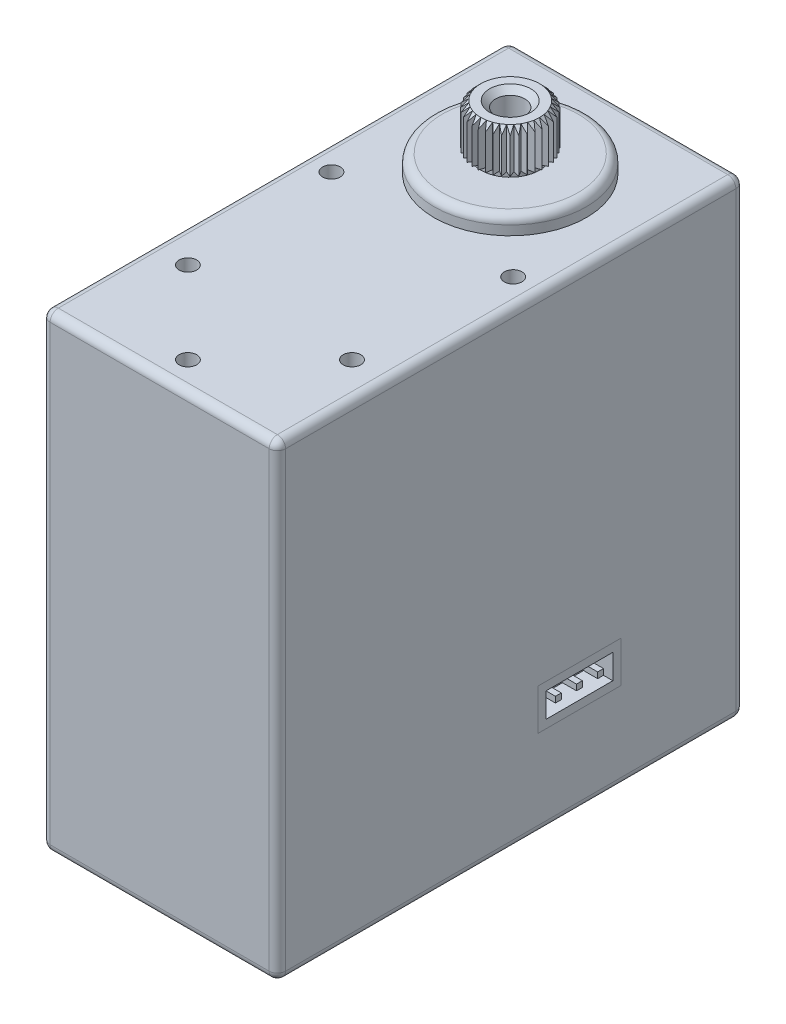
SolidWorks part; units mm, degrees
ref_plane "Alzado" through (0, 0, 0) normal (0, 0, 1) x (1, 0, 0)
ref_plane "Planta" through (0, 0, 0) normal (0, 1, 0) x (1, 0, 0)
ref_plane "Vista lateral" through (0, 0, 0) normal (1, 0, 0) x (0, 0, -1)
sketch "Croquis2" plane through (0, 0, 0) normal (0, 1, 0) x (1, 0, 0)
  line L0 (0, 0) -> (0, -27.5) construction
  line L1 (0, 7.5) -> (0, 9.91) construction
  line L2 (0, -7.5) -> (7.75, -7.5) construction
  line L3 (0, -20.5) -> (7, -20.5) construction
  line L4 (0, 0) -> (0, 7.5) construction
  line L5 (0, 7.5) -> (7.5, 7.5)
  line L6 (0, -27.5) -> (0, -29.91) construction
  line L7 (-10.045, -29.91) -> (10.045, -29.91)
  line L8 (-10.045, 9.91) -> (10.045, 9.91)
  line L9 (10.045, -29.91) -> (10.045, 9.91)
  line L10 (-10.045, -29.91) -> (-10.045, 9.91)
  circle A0 centre (0, 0) radius 3
  circle A3 centre (0, 0) radius 6.5
  circle A4 centre (7, -20.5) radius 0.75
  circle A6 centre (7.5, 7.5) radius 0.75
  circle A10 centre (0, -27.5) radius 0.75
  circle A11 centre (7.75, -7.5) radius 0.75
  circle A13 centre (-7, -20.5) radius 0.75
  circle A14 centre (-7.75, -7.5) radius 0.75
  dimension "D1" = 27.5
  dimension "D2" = 6
  dimension "D3" = 7
  dimension "D4" = 13
  dimension "D7" = 13
  dimension "D5" = 1.5
  dimension "D10" = 1.5
  dimension "D11" = 2.41
  dimension "D12" = 1.5
  dimension "D13" = 2.41
  dimension "D9" = 1.5
  dimension "D6" = 7
  dimension "D8" = 7.5
  dimension "D14" = 10.045
  dimension "D15" = 10.045
  dimension "D16" = 7.75
extrude "Saliente-Extruir1" add sketch "Croquis2" along normal blind 5.4 contours A0 region at (0, 0, 0)
extrude "Saliente-Extruir2" add sketch "Croquis2<4>" along normal blind 1.5 contours A3 region at (-6.3162, 0, 0)
sketch "Croquis2<4>" plane through (0, 0, 0) normal (0, 1, 0) x (1, 0, 0) same geometry as "Croquis2"
extrude "Saliente-Extruir3" add sketch "Croquis2<6>" against normal blind 40 separate body contours L10 L7 L9 L8 A14 A11 A10 A6 A4 A3 A13 | A10 | A4 | A13 | A11 | A14 | A6 | A3 A0 | A0 region at (-0.0202, 0, 11.9783) region at (0, 0, 0) region at (-6.3162, 0, 0) region at (7, 0, 20.5) region at (7.5, 0, -6.7712) region at (0, 0, 27.5) region at (7.75, 0, 7.5) region at (-7, 0, 20.5) region at (-7.75, 0, 7.5)
sketch "Croquis2<6>" plane through (0, 0, 0) normal (0, 1, 0) x (1, 0, 0) same geometry as "Croquis2"
extrude "Cortar-Extruir1" cut sketch "Croquis2<7>" against normal blind 2 contours A10 | A4 | A13 | A14 | A11 region at (7, 0, 20.5) region at (0, 0, 27.5) region at (7.75, 0, 7.5) region at (-7, 0, 20.5) region at (-7.75, 0, 7.5)
sketch "Croquis2<7>" plane through (0, 0, 0) normal (0, 1, 0) x (1, 0, 0) same geometry as "Croquis2"
extrude "Saliente-Extruir4" add sketch "Croquis2<8>" against normal blind 41.5 contours A3
sketch "Croquis2<8>" plane through (0, 0, 0) normal (0, 1, 0) x (1, 0, 0) same geometry as "Croquis2"
extrude "Saliente-Extruir5" add sketch "Croquis2<10>" against normal blind 45.7 contours A0
sketch "Croquis2<10>" plane through (0, 0, 0) normal (0, 1, 0) x (1, 0, 0) same geometry as "Croquis2"
sketch "Croquis3" plane through (0, -40, 0) normal (0, -1, 0) x (1, 0, 0)
  line L0 (0, 0) -> (0, 27.5) construction
  line L1 (0, 27.5) -> (-7.5, 27.5) construction
  line L2 (-7.5, -7.5) -> (-10.045, -7.5) construction
  line L3 (-10.045, 29.91) -> (-10.045, -9.91) construction
  line L4 (-7.5, -7.5) -> (-7.5, -9.91) construction
  line L5 (-10.045, -9.91) -> (10.045, -9.91) construction
  circle A0 centre (-7.5, 12.5) radius 0.75
  circle A1 centre (-7.5, -7.5) radius 0.75
  circle A2 centre (-7.5, 27.5) radius 0.75
  circle A3 centre (7.5, -7.5) radius 0.75
  circle A4 centre (7.5, 12.5) radius 0.75
  circle A5 centre (7.5, 27.5) radius 0.75
  dimension "D3" = 1.5
  dimension "D4" = 1.5
  dimension "D5" = 1.5
  dimension "D1" = 27.5
  dimension "D2" = 7.5
  dimension "D6" = 7.5
  dimension "D7" = 15
  dimension "D8" = 20
  dimension "D9" = 7.5
extrude "Cortar-Extruir2" cut sketch "Croquis3" against normal blind 2
sketch "Croquis5" plane through (0, 0, -9.91) normal (0, 0, -1) x (-1, 0, 0)
  line L0 (-10.045, -40) -> (-10.045, 0) construction
  line L1 (-3.545, -29) -> (3.545, -29)
  line L2 (-3.545, -29) -> (-3.545, -32.5)
  line L3 (-3.545, -32.5) -> (3.545, -32.5)
  line L4 (3.545, -29) -> (3.545, -32.5)
  line L5 (-6.5, -40) -> (6.5, -40) construction
  line L6 (10.045, -40) -> (10.045, 0) construction
  line L7 (-2.845, -31.8) -> (2.845, -31.8)
  line L8 (2.845, -29.7) -> (2.845, -31.8)
  line L9 (-2.845, -29.7) -> (2.845, -29.7)
  line L10 (-2.845, -29.7) -> (-2.845, -31.8)
  line L12 (-10.045, -29) -> (10.045, -29)
  line L13 (-10.045, -29) -> (-10.045, -12)
  line L14 (-10.045, -12) -> (10.045, -12)
  line L15 (10.045, -29) -> (10.045, -12)
  dimension "D1" = 6.5
  dimension "D2" = 7.5
  dimension "D3" = 6.5
  dimension "D4" = 3.5
  dimension "D5" = 17
extrude "Cortar-Extruir5" cut sketch "Croquis5" against normal blind 2 contours L9 L10 L7 L8 | L4 L1 L2 L3 L10 L9 L8 L7 region at (0, -29.0791, -9.91) region at (0, -30.75, -9.91)
extrude "Saliente-Extruir6" add sketch "Croquis5<4>" against normal blind 2 separate body contours L4 L1 L2 L3 L10 L9 L8 L7 region at (0, -29.0791, -9.91)
sketch "Croquis5<4>" plane through (0, 0, -9.91) normal (0, 0, -1) x (-1, 0, 0) same geometry as "Croquis5"
sketch "Croquis8" plane through (-10.045, 0, 0) normal (-1, 0, 0) x (0, 0, 1)
  line L0 (-9.91, -29) -> (-9.91, -12) construction
  line L1 (-9.91, -29) -> (0.59, -29)
  line L2 (-9.91, -29) -> (-9.91, -12)
  line L3 (-9.91, -12) -> (29.91, -12)
  line L4 (29.91, -29) -> (29.91, -12)
  line L5 (-9.91, -29) -> (-9.91, -32.5) construction
  line L6 (29.91, -40) -> (29.91, 0) construction
  line L7 (-9.91, -29.7) -> (-9.91, -31.8) construction
  line L9 (0.59, -29) -> (0.59, -32.5)
  line L10 (0.59, -32.5) -> (7.68, -32.5)
  line L11 (7.68, -29) -> (7.68, -32.5)
  line L12 (7.68, -29) -> (29.91, -29)
  line L13 (0.59, -29) -> (7.68, -29)
  line L14 (6.98, -29.7) -> (6.98, -31.8)
  line L15 (1.29, -31.8) -> (6.98, -31.8)
  line L16 (1.29, -29.7) -> (1.29, -31.8)
  line L17 (1.29, -29.7) -> (6.98, -29.7)
  dimension "D1" = 3.5
  dimension "D2" = 7.09
  dimension "D3" = 10.5
extrude "Cortar-Extruir6" cut sketch "Croquis8" against normal blind 2 contours L13 L9 L10 L11 L16 L17 L14 L15 | L17 L16 L15 L14 region at (-10.045, -29.0791, 4.135) region at (-10.045, -30.75, 4.135)
extrude "Saliente-Extruir9" add sketch "Croquis8<6>" against normal blind 2 separate body contours L13 L9 L10 L11 L16 L17 L14 L15 region at (-10.045, -29.0791, 4.135)
sketch "Croquis8<6>" plane through (-10.045, 0, 0) normal (-1, 0, 0) x (0, 0, 1) same geometry as "Croquis8"
mirror "Simetría1" about plane through (0, 0, 0) normal (1, 0, 0) of "Cortar-Extruir6"
mirror "Simetría4" about plane through (0, 0, 0) normal (1, 0, 0) of bodies 116
fillet "Redondeo1" radius 0.7 12 edges at (-10.045, -20, 29.91) (0, -40, 29.91) (10.045, -40, 10) (-10.045, -40, 10) (0, -40, -9.91) (0, 0, -9.91) (10.045, 0, 10) (0, 0, 29.91) (-10.045, 0, 10) (-10.045, -20, -9.91) (10.045, -20, 29.91) (10.045, -20, -9.91)
fillet "Redondeo2" radius 0.7 3 edges at (0, -41.5, 6.5) (0, -41.5, 3) (0, 1.5, 6.5)
chamfer "Chaflán1" distance 0.5 angle 45 1 edges at (0, 5.4, 3)
sketch "Croquis9" plane through (0, 5.4, 0) normal (0, 1, 0) x (1, 0, 0)
  line L0 (0, 0) -> (0, 3) construction
  line L1 (0, 0) -> (0.2615, 2.9886) construction
  line L2 (0, 2.5) -> (0.2615, 2.9886)
  line L3 (0, 2.5) -> (-0.2615, 2.9886)
  line L4 (0, 0) -> (-0.2615, 2.9886) construction
  line L5 (0.4341, 2.462) -> (0.7765, 2.8978)
  line L6 (0.4341, 2.462) -> (0.2615, 2.9886)
  line L7 (0.8551, 2.3492) -> (1.2679, 2.7189)
  line L8 (0.8551, 2.3492) -> (0.7765, 2.8978)
  line L9 (1.25, 2.1651) -> (1.7207, 2.4575)
  line L10 (1.25, 2.1651) -> (1.2679, 2.7189)
  line L11 (1.607, 1.9151) -> (2.1213, 2.1213)
  line L12 (1.607, 1.9151) -> (1.7207, 2.4575)
  line L13 (1.9151, 1.607) -> (2.4575, 1.7207)
  line L14 (1.9151, 1.607) -> (2.1213, 2.1213)
  line L15 (2.1651, 1.25) -> (2.7189, 1.2679)
  line L16 (2.1651, 1.25) -> (2.4575, 1.7207)
  line L17 (2.3492, 0.8551) -> (2.8978, 0.7765)
  line L18 (2.3492, 0.8551) -> (2.7189, 1.2679)
  line L19 (2.462, 0.4341) -> (2.9886, 0.2615)
  line L20 (2.462, 0.4341) -> (2.8978, 0.7765)
  line L21 (2.5, 0) -> (2.9886, -0.2615)
  line L22 (2.5, 0) -> (2.9886, 0.2615)
  line L23 (2.462, -0.4341) -> (2.8978, -0.7765)
  line L24 (2.462, -0.4341) -> (2.9886, -0.2615)
  line L25 (2.3492, -0.8551) -> (2.7189, -1.2679)
  line L26 (2.3492, -0.8551) -> (2.8978, -0.7765)
  line L27 (2.1651, -1.25) -> (2.4575, -1.7207)
  line L28 (2.1651, -1.25) -> (2.7189, -1.2679)
  line L29 (1.9151, -1.607) -> (2.1213, -2.1213)
  line L30 (1.9151, -1.607) -> (2.4575, -1.7207)
  line L31 (1.607, -1.9151) -> (1.7207, -2.4575)
  line L32 (1.607, -1.9151) -> (2.1213, -2.1213)
  line L33 (1.25, -2.1651) -> (1.2679, -2.7189)
  line L34 (1.25, -2.1651) -> (1.7207, -2.4575)
  line L35 (0.8551, -2.3492) -> (0.7765, -2.8978)
  line L36 (0.8551, -2.3492) -> (1.2679, -2.7189)
  line L37 (0.4341, -2.462) -> (0.2615, -2.9886)
  line L38 (0.4341, -2.462) -> (0.7765, -2.8978)
  line L39 (0, -2.5) -> (-0.2615, -2.9886)
  line L40 (0, -2.5) -> (0.2615, -2.9886)
  line L41 (-0.4341, -2.462) -> (-0.7765, -2.8978)
  line L42 (-0.4341, -2.462) -> (-0.2615, -2.9886)
  line L43 (-0.8551, -2.3492) -> (-1.2679, -2.7189)
  line L44 (-0.8551, -2.3492) -> (-0.7765, -2.8978)
  line L45 (-1.25, -2.1651) -> (-1.7207, -2.4575)
  line L46 (-1.25, -2.1651) -> (-1.2679, -2.7189)
  line L47 (-1.607, -1.9151) -> (-2.1213, -2.1213)
  line L48 (-1.607, -1.9151) -> (-1.7207, -2.4575)
  line L49 (-1.9151, -1.607) -> (-2.4575, -1.7207)
  line L50 (-1.9151, -1.607) -> (-2.1213, -2.1213)
  line L51 (-2.1651, -1.25) -> (-2.7189, -1.2679)
  line L52 (-2.1651, -1.25) -> (-2.4575, -1.7207)
  line L53 (-2.3492, -0.8551) -> (-2.8978, -0.7765)
  line L54 (-2.3492, -0.8551) -> (-2.7189, -1.2679)
  line L55 (-2.462, -0.4341) -> (-2.9886, -0.2615)
  line L56 (-2.462, -0.4341) -> (-2.8978, -0.7765)
  line L57 (-2.5, 0) -> (-2.9886, 0.2615)
  line L58 (-2.5, 0) -> (-2.9886, -0.2615)
  line L59 (-2.462, 0.4341) -> (-2.8978, 0.7765)
  line L60 (-2.462, 0.4341) -> (-2.9886, 0.2615)
  line L61 (-2.3492, 0.8551) -> (-2.7189, 1.2679)
  line L62 (-2.3492, 0.8551) -> (-2.8978, 0.7765)
  line L63 (-2.1651, 1.25) -> (-2.4575, 1.7207)
  line L64 (-2.1651, 1.25) -> (-2.7189, 1.2679)
  line L65 (-1.9151, 1.607) -> (-2.1213, 2.1213)
  line L66 (-1.9151, 1.607) -> (-2.4575, 1.7207)
  line L67 (-1.607, 1.9151) -> (-1.7207, 2.4575)
  line L68 (-1.607, 1.9151) -> (-2.1213, 2.1213)
  line L69 (-1.25, 2.1651) -> (-1.2679, 2.7189)
  line L70 (-1.25, 2.1651) -> (-1.7207, 2.4575)
  line L71 (-0.8551, 2.3492) -> (-0.7765, 2.8978)
  line L72 (-0.8551, 2.3492) -> (-1.2679, 2.7189)
  line L73 (-0.4341, 2.462) -> (-0.2615, 2.9886)
  line L74 (-0.4341, 2.462) -> (-0.7765, 2.8978)
  circle A0 centre (0, 0) radius 3 construction
  circle A2 centre (0, 0) radius 2.2 construction
  circle A4 centre (0, 0) radius 3 construction
  circle A5 centre (0, 0) radius 2.5
  circle A7 centre (0, 0) radius 5.8
  point P11 (0, 0)
  point P120 (0, 0)
  point P124 (0, 0)
  dimension "D1" = 4.4
  dimension "D2" = 5
  dimension "D3" = 36
extrude "Cortar-Extruir13" cut sketch "Croquis9" against normal blind 3.5 contours A7 L74 L73 L3 L2 L6 L5 L8 L7 L10 L9 L12 L11 L14 L13 L16 L15 L18 L17 L20 L19 L22 L21 L24 L23 L26 L25 L28 L27 L30 L29 L32 L31 L34 L33 L36 L35 L38 L37 L40 L39 L42 L41 L44 L43 L46 L45 L48 L47 L50 region at (-5.636, 5.4, 0)
sketch "Croquis10" plane through (0, 1.9, 0) normal (0, 1, 0) x (1, 0, 0)
  circle A0 centre (0, 0) radius 3
  circle A1 centre (0, 0) radius 2.5
extrude "Cortar-Extruir15" cut sketch "Croquis10" against normal up to surface (0.4 mm away) up to face at (0, 1.5, 5.8)
sketch "Croquis11" plane through (0, 5.4, 0) normal (0, 1, 0) x (1, 0, 0)
  circle A0 centre (0, 0) radius 1.25
  dimension "D1" = 2.5
extrude "Cortar-Extruir16" cut sketch "Croquis11" against normal blind 4
chamfer "Chaflán2" distance 0.5 angle 45 1 edges at (0, 5.4, 1.25)
sketch "Croquis12" plane through (8.045, 0, 0) normal (1, 0, 0) x (0, 0, -1)
  line L0 (-1.29, -30.75) -> (-6.98, -30.75) construction
  line L1 (-1.29, -29.7) -> (-1.29, -31.8) construction
  line L2 (-6.98, -29.7) -> (-6.98, -31.8) construction
  line L3 (-4.135, -30.75) -> (-4.135, -31.8) construction
  line L4 (-2.085, -30.5) -> (-2.585, -30.5)
  line L5 (-2.085, -30.5) -> (-2.085, -31)
  line L6 (-2.085, -31) -> (-2.585, -31)
  line L7 (-2.585, -30.5) -> (-2.585, -31)
  line L8 (-2.085, -30.5) -> (-2.585, -31) construction
  line L9 (-2.085, -31) -> (-2.585, -30.5) construction
  line L10 (-3.885, -30.5) -> (-4.385, -30.5)
  line L11 (-3.885, -30.5) -> (-3.885, -31)
  line L12 (-3.885, -31) -> (-4.385, -31)
  line L13 (-4.385, -30.5) -> (-4.385, -31)
  line L14 (-3.885, -30.5) -> (-4.385, -31) construction
  line L15 (-3.885, -31) -> (-4.385, -30.5) construction
  line L16 (-1.29, -31.8) -> (-6.98, -31.8) construction
  line L17 (-6.185, -31) -> (-5.685, -31)
  line L18 (-6.185, -30.5) -> (-6.185, -31)
  line L19 (-6.185, -30.5) -> (-5.685, -30.5)
  line L20 (-5.685, -30.5) -> (-5.685, -31)
  point P6 (-2.335, -30.75)
  point P11 (-4.135, -30.75)
  dimension "D1" = 1.8
  dimension "D2" = 0.5
  dimension "D3" = 0.5
  dimension "D4" = 0.5
  dimension "D5" = 0.5
extrude "Saliente-Extruir13" add sketch "Croquis12" along normal blind 2 separate body
mirror "Simetría5" about plane through (0, 0, 0) normal (1, 0, 0) of "Saliente-Extruir13"
sketch "Croquis13" plane through (0, 0, -7.91) normal (0, 0, -1) x (-1, 0, 0)
  line L0 (-2.845, -30.75) -> (2.845, -30.75) construction
  line L1 (-2.845, -29.7) -> (-2.845, -31.8) construction
  line L2 (2.845, -29.7) -> (2.845, -31.8) construction
  line L3 (0, -29.7) -> (0, -31.8) construction
  line L4 (-2.845, -29.7) -> (2.845, -29.7) construction
  line L5 (-2.845, -31.8) -> (2.845, -31.8) construction
  line L6 (-1.55, -31) -> (-2.05, -31)
  line L7 (-0.25, -31) -> (0.25, -31)
  line L8 (-0.25, -31) -> (-0.25, -30.5)
  line L9 (-0.25, -30.5) -> (0.25, -30.5)
  line L10 (0.25, -31) -> (0.25, -30.5)
  line L11 (-0.25, -31) -> (0.25, -30.5) construction
  line L12 (-0.25, -30.5) -> (0.25, -31) construction
  line L13 (1.55, -31) -> (2.05, -31)
  line L14 (1.55, -31) -> (1.55, -30.5)
  line L15 (1.55, -30.5) -> (2.05, -30.5)
  line L16 (2.05, -31) -> (2.05, -30.5)
  line L17 (1.55, -31) -> (2.05, -30.5) construction
  line L18 (1.55, -30.5) -> (2.05, -31) construction
  line L19 (-2.05, -31) -> (-2.05, -30.5)
  line L20 (-1.55, -30.5) -> (-2.05, -30.5)
  line L21 (-1.55, -31) -> (-1.55, -30.5)
  point P12 (0, -30.75)
  point P17 (1.8, -30.75)
  dimension "D1" = 0.5
  dimension "D2" = 0.5
  dimension "D3" = 0.5
  dimension "D4" = 0.5
  dimension "D5" = 1.8
extrude "Saliente-Extruir14" add sketch "Croquis13" along normal blind 2 separate body
ref_plane "Plane1" through (0, -20, 0) normal (0, -1, 0) x (-1, 0, 0)
ref_plane "Plane2" through (0, 0, 0) normal (-1, 0, 0) x (0, 0, 1)
